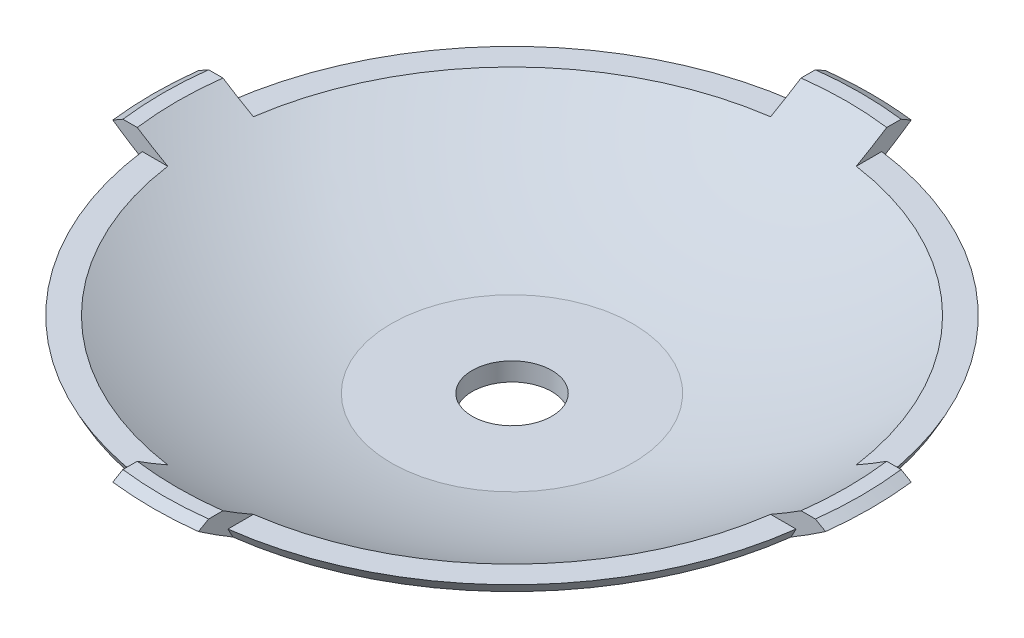
SolidWorks part; units mm, degrees
ref_plane "Front Plane" through (0, 0, 0) normal (0, 0, 1) x (1, 0, 0)
ref_plane "Top Plane" through (0, 0, 0) normal (0, 1, 0) x (1, 0, 0)
ref_plane "Right Plane" through (0, 0, 0) normal (1, 0, 0) x (0, 0, -1)
sketch "Sketch1" plane through (0, 0, 0) normal (0, 0, 1) x (1, 0, 0)
  line L0 (0, 0) -> (0, 17)
  line L1 (0, 17) -> (-60, 17)
  line L2 (-20, 0) -> (0, 0)
  arc A1 (-60, 17) -> (-20, 0) centre (-1.8207, 98.3337) ccw
  dimension "D4" = 100
  dimension "D1" = 20
  dimension "D2" = 17
  dimension "D3" = 60
revolve "Revolve1" add sketch "Sketch1" angle 360 about L0
shell "Shell1" thickness 3
sketch "Sketch2" plane through (0, 17, 0) normal (0, 1, 0) x (1, 0, 0)
  line L0 (0, 60) -> (0, 0) construction
  line L1 (0, 0) -> (60, 0) construction
  line L2 (7, 59.5903) -> (7, 7)
  line L3 (7, 7) -> (59.5903, 7)
  line L4 (7, 60) -> (7, 7) construction
  line L5 (7, 7) -> (60, 7) construction
  circle A0 centre (0, 0) radius 60 construction
  arc A1 (59.5903, 7) -> (7, 59.5903) centre (0, 0) ccw
  dimension "D1" = 7
extrude "Cut-Extrude1" cut sketch "Sketch2" against normal blind 3
pattern_circular "CirPattern1" count 4 over 360 about axis through (0, 0, 0) along (0, 1, 0) of "Cut-Extrude1"
sketch "Sketch3" plane through (0, 3, 0) normal (0, 1, 0) x (1, 0, 0)
  circle A0 centre (0, 0) radius 6.5
  dimension "D1" = 13
extrude "Cut-Extrude2" cut sketch "Sketch3" against normal blind 3
chamfer "Chamfer1" distance 3 angle 30 8 edges at (39.2863, 14, -39.2863) (39.2863, 14, 39.2863) (-39.2863, 14, -39.2863) (-39.2863, 14, 39.2863) (-60, 17, 0) (0, 17, -60) (60, 17, 0) (0, 17, 60)
